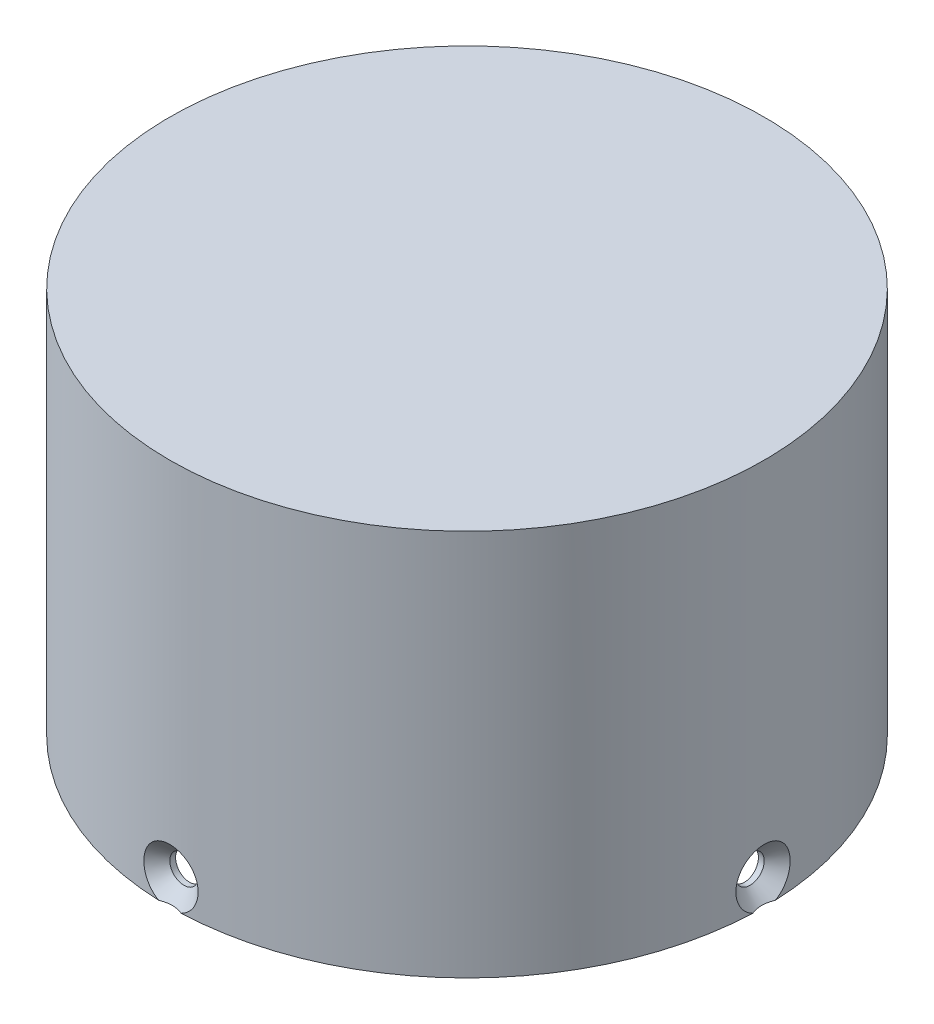
SolidWorks part; units mm, degrees
ref_plane "Front Plane" through (0, 0, 0) normal (0, 0, 1) x (1, 0, 0)
ref_plane "Top Plane" through (0, 0, 0) normal (0, 1, 0) x (1, 0, 0)
ref_plane "Right Plane" through (0, 0, 0) normal (1, 0, 0) x (0, 0, -1)
sketch "Sketch3" plane through (0, 0, 0) normal (0, 1, 0) x (1, 0, 0)
  circle A0 centre (0, 0) radius 23.049
  dimension "D1" = 46.098
extrude "Boss-Extrude3" add sketch "Sketch3" along normal blind 30
sketch "Sketch4" plane through (0, 0, 0) normal (0, -1, 0) x (1, 0, 0)
  circle A0 centre (0, 0) radius 21.525
  dimension "D1" = 43.05
extrude "Cut-Extrude1" cut sketch "Sketch4" against normal blind 27.46
hole_wizard "CSK for M2 Flat Head Machine Screw2" positions "3DSketch1" profile "Sketch5" countersink size "M2" standard "ANSI Metric" end condition up to next
sketch3d "3DSketch1"
  point P0 (23.049, 2, 0)
  dimension "D1" = 2
sketch "Sketch5" plane through (23.049, 2, 0) normal (0, 1, 0) x (0, 0, -1)
  line L0 (0, 0) -> (0, 1.524)
  line L1 (0, 1.524) -> (1.1, 1.524)
  line L2 (1.1, 1.524) -> (1.1, 1.1)
  line L3 (1.1, 1.1) -> (2.2, 0)
  line L5 (2.2, 0) -> (0, 0)
  line L6 (-1.1, 1.1) -> (-2.2, 0) construction
  line L11 (0, -6.35) -> (0, 107.95) construction
  dimension "Thru Hole Dia." = 2.2
  dimension "Thru Hole Depth" = 1.524
  dimension "Near C'Sink Dia." = 4.4
  dimension "Near C'Sink Angle" = 90
ref_axis "Axis1" through (0, 27.46, 0) along (0, -1, 0)
pattern_circular "CirPattern1" count 4 over 360 about axis through (0, 27.46, 0) along (0, -1, 0) of "CSK for M2 Flat Head Machine Screw2"
